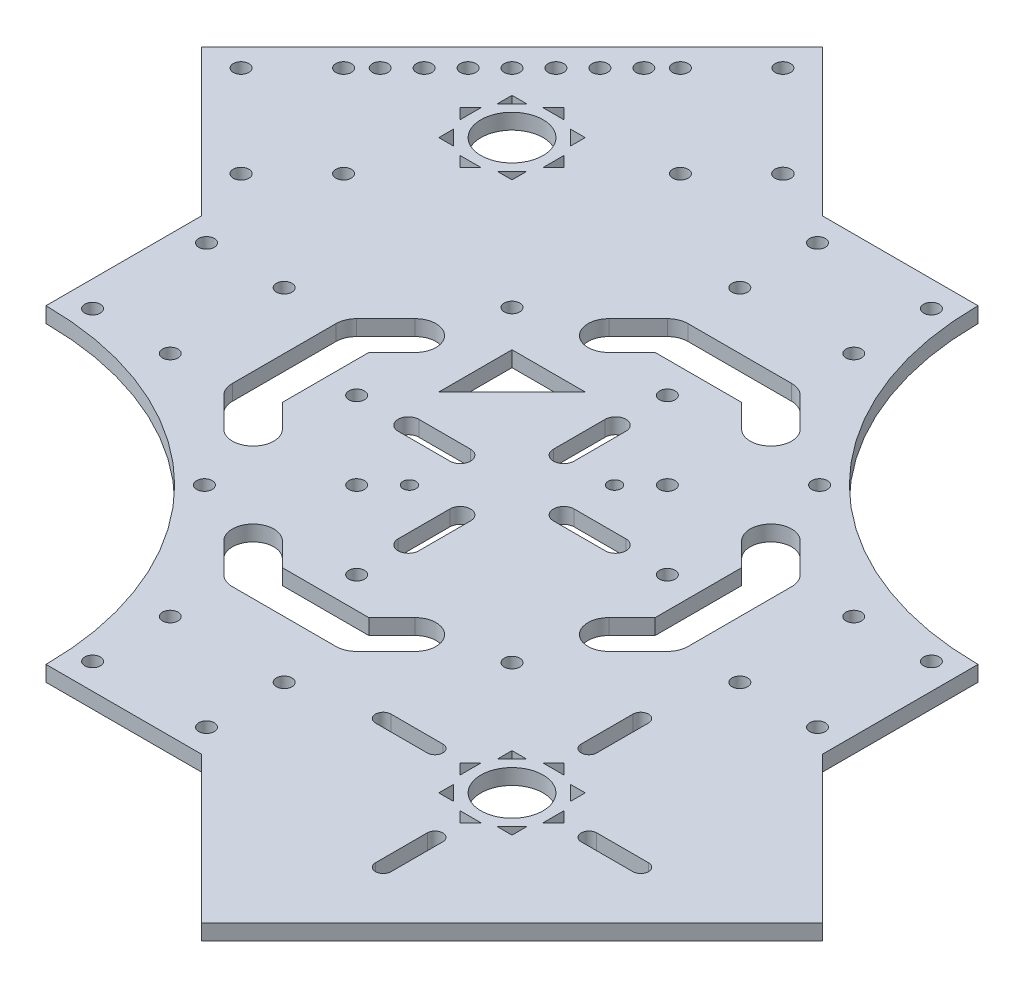
SolidWorks part; units mm, degrees
ref_plane "前视基准面" through (0, 0, 0) normal (0, 0, 1) x (1, 0, 0)
ref_plane "上视基准面" through (0, 0, 0) normal (0, 1, 0) x (1, 0, 0)
ref_plane "右视基准面" through (0, 0, 0) normal (1, 0, 0) x (0, 0, -1)
sketch "草图1" plane through (0, 0, 0) normal (0, 1, 0) x (1, 0, 0)
  line L0 (0, 0) -> (0, 75)
  line L1 (0, 0) -> (75, 0)
  line L2 (0, 0) -> (0, -75)
  line L3 (0, 0) -> (-75, 0)
  line L4 (0, 75) -> (15, 75)
  line L5 (0, 75) -> (-15, 75)
  line L6 (75, 0) -> (75, 15)
  line L7 (75, 0) -> (75, -15)
  line L8 (0, -75) -> (15, -75)
  line L9 (0, -75) -> (-15, -75)
  line L10 (-75, 0) -> (-75, -15)
  line L11 (-75, 0) -> (-75, 15)
  line L12 (75, 0) -> (70, 0)
  arc A0 (-75, 15) -> (-15, 75) centre (-75, 75) ccw
  arc A1 (15, 75) -> (75, 15) centre (75, 75) ccw
  arc A2 (75, -15) -> (15, -75) centre (75, -75) ccw
  arc A3 (-15, -75) -> (-75, -15) centre (-75, -75) ccw
  circle A4 centre (-11, 70) radius 1.25
  circle A5 centre (11, 70) radius 1.25
  circle A6 centre (70, -11) radius 1.25
  circle A7 centre (70, 11) radius 1.25
  circle A8 centre (-11, -70) radius 1.25
  circle A9 centre (11, -70) radius 1.25
  circle A10 centre (-70, 11) radius 1.25
  circle A11 centre (-70, -11) radius 1.25
  point P9 (0, 0)
  point P21 (0, 0)
  point P32 (0, 0)
  point P35 (0, 0)
  point P44 (0, 0)
  dimension "D1" = 4
extrude "凸台-拉伸1" add sketch "草图1" along normal blind 3 contours A2 L7 L1 L2 L8 A9 A6 | A3 L9 L2 L3 L10 A11 A8 | A0 L11 L3 L0 L5 A4 A10 | A1 L4 L0 L1 L6 A7 A5 region at (-25.2829, 0, -25.2829) region at (25.2829, 0, -25.2829) region at (25.2829, 0, 25.2829) region at (-25.2829, 0, 25.2829)
sketch "草图2" plane through (0, 0, 0) normal (0, -1, 0) x (1, 0, 0)
  line L0 (0, 0) -> (-32.5736, -32.5736)
  line L1 (0, 0) -> (32.5736, -32.5736)
  line L2 (-31.4663, 0.3536) -> (-0.3536, 31.4663)
  line L3 (31.4663, -0.3536) -> (-0.3536, 31.4663)
  line L4 (0.3536, -31.4663) -> (31.4663, -0.3536)
  line L5 (0.3536, -31.4663) -> (-31.4663, 0.3536)
  arc A0 (-15, -75) -> (-75, -15) centre (-75, -75) ccw construction
  circle A2 centre (0.3536, -31.4663) radius 1.5
  circle A3 centre (31.4663, -0.3536) radius 1.5
  circle A4 centre (-0.3536, 31.4663) radius 1.5
  circle A5 centre (-31.4663, 0.3536) radius 1.5
  point P12 (-15.5563, -15.5563)
  point P16 (-15.9099, 15.9099)
  point P17 (15.9099, -15.9099)
extrude "切除-拉伸1" cut sketch "草图2" against normal blind 3 contours A3 | A2 | A5 | A4
sketch "草图3" plane through (0, 3, 0) normal (0, 1, 0) x (1, 0, 0)
  line L0 (0.3536, 31.4663) -> (-31.4663, -0.3536)
  line L1 (-15.5563, 15.5563) -> (-22.6274, 22.6274)
  line L2 (-15.5563, 15.5563) -> (-12.0208, 19.0919)
  line L3 (-15.5563, 15.5563) -> (-19.0919, 12.0208)
  line L4 (-19.0919, 12.0208) -> (-22.6274, 22.6274)
  line L5 (-12.0208, 19.0919) -> (-22.6274, 22.6274)
extrude "切除-拉伸2" cut sketch "草图3" against normal blind 3 contours L0 L5 L1 | L4 L0 L1 region at (-16.7349, 3, -19.0919) region at (-19.0919, 3, -16.7349)
sketch "草图4" plane through (0, 3, 0) normal (0, 1, 0) x (1, 0, 0)
  line L0 (31.4663, 0.3536) -> (-0.3536, -31.4663)
  line L1 (0, 0) -> (21.2132, -21.2132)
  line L2 (28.2843, -14.1421) -> (14.1421, -28.2843)
  line L3 (14.1421, -28.2843) -> (28.2843, -14.1421) construction
  line L4 (8.4817, -22.6239) -> (22.6239, -8.4817)
  line L5 (19.8025, -33.9447) -> (33.9447, -19.8025)
  arc A0 (8.4817, -22.6239) -> (19.8025, -33.9447) centre (14.1421, -28.2843) ccw
  arc A1 (33.9447, -19.8025) -> (22.6239, -8.4817) centre (28.2843, -14.1421) ccw
  point P9 (21.2132, -21.2132)
extrude "切除-拉伸3" cut sketch "草图4" against normal blind 3 contours L5 A1 L0 A0 region at (21.2143, 3, 21.2143)
sketch "草图5" plane through (0, 3, 0) normal (0, 1, 0) x (1, 0, 0)
  line L0 (-12.0208, 19.0919) -> (-8.4853, 22.6274)
  line L1 (-8.4853, 22.6274) -> (-22.6274, 22.6274)
  line L2 (-19.0919, 12.0208) -> (-22.6274, 8.4853)
  line L3 (-22.6274, 8.4853) -> (-22.6274, 22.6274)
  line L4 (-12.0208, 19.0919) -> (-22.6274, 22.6274)
  line M28 (-19.0919, 12.0208) -> (-22.6274, 22.6274)
extrude "切除-拉伸4" cut sketch "草图5" against normal blind 10 contours L3 L2 M28 | L4 L0 L1 region at (-21.4489, 3, -14.3778)
sketch "草图6" plane through (0, 3, 0) normal (0, 1, 0) x (1, 0, 0)
  line L0 (0, 0) -> (-28.2843, -28.2843)
  line L1 (-28.2843, -28.2843) -> (-35.3553, -21.2132)
  line L2 (0, 0) -> (-22.6274, 22.6274)
  circle A0 centre (-35.3553, -21.2132) radius 1.5
  circle A1 centre (-21.2132, -35.3553) radius 1.5
  circle A2 centre (35.3553, 21.2132) radius 1.5
  circle A3 centre (21.2132, 35.3553) radius 1.5
extrude "切除-拉伸5" cut sketch "草图6" against normal blind 10 contours A1 | A0 | A2 | A3
sketch "草图7" plane through (0, 3, 0) normal (0, 1, 0) x (1, 0, 0)
  circle A0 centre (-29.6985, 29.6985) radius 1.5
  circle A1 centre (29.6985, 29.6985) radius 1.5
  circle A2 centre (29.6985, -29.6985) radius 1.5
  circle A3 centre (-29.6985, -29.6985) radius 1.5
  point P11 (0, 0)
  dimension "D1" = 4
extrude "切除-拉伸8" cut sketch "草图7" against normal blind 10
sketch "草图8" plane through (0, 3, 0) normal (0, 1, 0) x (1, 0, 0)
  circle A0 centre (-11, 55) radius 1.5
  circle A1 centre (11, 55) radius 1.5
  circle A2 centre (55, 11) radius 1.5
  circle A3 centre (55, -11) radius 1.5
  circle A4 centre (11, -55) radius 1.5
  circle A5 centre (-11, -55) radius 1.5
  circle A6 centre (-55, -11) radius 1.5
  circle A7 centre (-55, 11) radius 1.5
  point P21 (0, 0)
  dimension "D1" = 4
extrude "切除-拉伸9" cut sketch "草图8" against normal blind 10
sketch "草图9" plane through (0, 3, 0) normal (0, 1, 0) x (1, 0, 0)
  circle A0 centre (0, 0) radius 15
extrude "切除-拉伸10" cut sketch "草图9" against normal blind 10
sketch "草图11" plane through (0, 3, 0) normal (0, 1, 0) x (1, 0, 0)
  circle A0 centre (-35.3553, -21.2132) radius 1.5
  circle A2 centre (35.3553, 21.2132) radius 1.5
  circle A3 centre (21.2132, 35.3553) radius 1.5
  circle A4 centre (0.3536, 31.4663) radius 1.5
  circle A5 centre (31.4663, 0.3536) radius 1.5
  circle A6 centre (-0.3536, -31.4663) radius 1.5
  circle A7 centre (-31.4663, -0.3536) radius 1.5
  circle A8 centre (-21.2132, -35.3553) radius 1.5
extrude "凸台-拉伸3" add sketch "草图11" against normal blind 3
sketch "草图12" plane through (0, 3, 0) normal (0, 1, 0) x (1, 0, 0)
  line L0 (0, 0) -> (-40, 0)
  line L1 (-40, 0) -> (-40, 10)
  line L2 (-40, 0) -> (-40, -10)
  line L3 (-40, -10) -> (-40, 10) construction
  line L4 (-44, -10) -> (-44, 10)
  line L5 (-36, -10) -> (-36, 10)
  line L6 (-10, 40) -> (10, 40) construction
  line L7 (-10, 44) -> (10, 44)
  line L8 (-10, 36) -> (10, 36)
  line L9 (40, 10) -> (40, -10) construction
  line L10 (44, 10) -> (44, -10)
  line L11 (36, 10) -> (36, -10)
  line L12 (10, -40) -> (-10, -40) construction
  line L13 (10, -44) -> (-10, -44)
  line L14 (10, -36) -> (-10, -36)
  arc A0 (-44, -10) -> (-36, -10) centre (-40, -10) ccw
  arc A1 (-36, 10) -> (-44, 10) centre (-40, 10) ccw
  arc A2 (-10, 44) -> (-10, 36) centre (-10, 40) ccw
  arc A3 (10, 36) -> (10, 44) centre (10, 40) ccw
  arc A4 (44, 10) -> (36, 10) centre (40, 10) ccw
  arc A5 (36, -10) -> (44, -10) centre (40, -10) ccw
  arc A6 (10, -44) -> (10, -36) centre (10, -40) ccw
  arc A7 (-10, -36) -> (-10, -44) centre (-10, -40) ccw
  point P3 (-40, 0)
  point P13 (0, 40)
  point P20 (40, 0)
  point P27 (0, -40)
  point P34 (0, 0)
  dimension "D1" = 4
extrude "切除-拉伸12" cut sketch "草图12" against normal blind 3 contours L5 A1 L4 A0 | L8 A3 L7 A2 | L11 A5 L10 A4 | L14 A7 L13 A6 region at (-43.7088, 3, 0) region at (0, 3, -40) region at (40, 3, 0) region at (0, 3, 40)
sketch "草图14" plane through (0, 3, 0) normal (0, 1, 0) x (1, 0, 0)
  line L0 (22.8277, -8.285) -> (8.285, -22.8277) construction
  line L1 (19.8025, -33.9447) -> (33.9447, -19.8025) construction
  line L2 (8.285, -22.8277) -> (22.8277, -8.285)
  line L3 (22.8277, -8.285) -> (19.8025, -33.9447)
  line L4 (19.8025, -33.9447) -> (33.9447, -19.8025)
  arc A0 (8.285, -22.8277) -> (19.8025, -33.9447) centre (14.1421, -28.2843) ccw
  arc A1 (8.285, -22.8277) -> (19.8025, -33.9447) centre (14.1421, -28.2843) ccw construction
  arc A2 (33.9447, -19.8025) -> (22.8277, -8.285) centre (28.2843, -14.1421) ccw construction
  arc A3 (22.8277, -8.285) -> (32.1857, -7.1522) centre (28.2843, -14.1421) ccw
  circle A4 centre (28.2843, -14.1421) radius 8.005
extrude "凸台-拉伸4" add sketch "草图14" against normal blind 3 contours A3 A4 L3 | L2 A3 L3 | A3 L2 A0 L3 | A3 L3 L4 region at (14.6624, 3, 25.7239) region at (21.4582, 3, 13.3381) region at (24.21, 3, 25.4431) region at (28.7736, 3, 14.1998)
sketch "草图15" plane through (0, 3, 0) normal (0, 1, 0) x (1, 0, 0)
  circle A0 centre (0, 0) radius 15
extrude "凸台-拉伸5" add sketch "草图15" against normal blind 3
sketch "草图17" plane through (0, 3, 0) normal (0, 1, 0) x (1, 0, 0)
  line L0 (0, 0) -> (0, -20)
  line L1 (0, -20) -> (0, -10) construction
  line L2 (-2, -20) -> (-2, -10)
  line L3 (2, -20) -> (2, -10)
  line L4 (-20, 0) -> (-10, 0) construction
  line L5 (-20, 2) -> (-10, 2)
  line L6 (-20, -2) -> (-10, -2)
  line L7 (0, 20) -> (0, 10) construction
  line L8 (2, 20) -> (2, 10)
  line L9 (-2, 20) -> (-2, 10)
  line L10 (20, 0) -> (10, 0) construction
  line L11 (20, -2) -> (10, -2)
  line L12 (20, 2) -> (10, 2)
  arc A0 (-2, -20) -> (2, -20) centre (0, -20) ccw
  arc A1 (2, -10) -> (-2, -10) centre (0, -10) ccw
  arc A2 (-20, 2) -> (-20, -2) centre (-20, 0) ccw
  arc A3 (-10, -2) -> (-10, 2) centre (-10, 0) ccw
  arc A4 (2, 20) -> (-2, 20) centre (0, 20) ccw
  arc A5 (-2, 10) -> (2, 10) centre (0, 10) ccw
  arc A6 (20, -2) -> (20, 2) centre (20, 0) ccw
  arc A7 (10, 2) -> (10, -2) centre (10, 0) ccw
  point P3 (0, -15)
  point P13 (-15, 0)
  point P20 (0, 15)
  point P27 (15, 0)
  point P33 (0, 0)
  dimension "D1" = 4
extrude "切除-拉伸13" cut sketch "草图17" against normal blind 3 contours L8 A5 L9 A4 | L12 A7 L11 A6 | L3 A1 L2 A0 | L5 A3 L6 A2
sketch "草图18" plane through (0, 3, 0) normal (0, 1, 0) x (1, 0, 0)
  line L0 (0, 0) -> (-32.5736, 32.5736)
  line L1 (-32.5736, 32.5736) -> (-46.7157, 46.7157)
  line L2 (-50.2513, 50.2513) -> (-61.9773, 38.5252)
  line L3 (-46.7157, 46.7157) -> (-50.2513, 50.2513)
  line L4 (-61.9773, 38.5252) -> (-38.5252, 61.9773)
  line L5 (-38.5252, 61.9773) -> (-22.5002, 45.9523)
  line L6 (-61.9773, 38.5252) -> (-45.9523, 22.5002)
  arc A0 (-75, 15) -> (-15, 75) centre (-75, 75) ccw construction
  circle A1 centre (-67.9289, 67.9289) radius 30
  circle A2 centre (-75, 75) radius 60
extrude "凸台-拉伸7" add sketch "草图18" against normal blind 3 contours L4 A1 L2 | L2 A1 L3 | L3 A1 L4 | L6 A2 L1 A1 | L1 A2 L5 A1 region at (-46.4984, 3, -34.5306) region at (-34.5306, 3, -46.4984) region at (-53.277, 3, -44.3758) region at (-44.3758, 3, -53.277) region at (-68.7208, 3, -68.7208)
sketch "草图19" plane through (0, 3, 0) normal (0, 1, 0) x (1, 0, 0)
  line L0 (-61.9773, 38.5252) -> (-38.5252, 61.9773)
  line L1 (-50.2513, 50.2513) -> (-36.1091, 36.1091)
  line L2 (-36.1091, 36.1091) -> (-43.1802, 29.0381)
  line L3 (-36.1091, 36.1091) -> (-29.0381, 43.1802)
  line L4 (-29.0381, 43.1802) -> (-37.1408, 51.2829)
  line L5 (-37.1408, 51.2829) -> (-51.2829, 37.1408)
  line L6 (-51.2829, 37.1408) -> (-43.1802, 29.0381)
  circle A1 centre (-67.9289, 67.9289) radius 35
  circle A2 centre (-67.9289, 67.9289) radius 45
extrude "切除-拉伸14" cut sketch "草图19" against normal blind 3 contours L1 A2 L4 A1 | L6 A2 L1 A1 region at (-36.3949, 3, -43.5045) region at (-43.5045, 3, -36.3949)
sketch "草图21" plane through (0, 3, 0) normal (0, 1, 0) x (1, 0, 0)
  line L0 (-61.9773, 38.5252) -> (-38.5252, 61.9773)
  line L1 (-67.9289, 67.9289) -> (-53.7868, 53.7868)
  line L2 (-82.0711, 82.0711) -> (-75, 75)
  line L3 (-67.9289, 67.9289) -> (-82.0711, 82.0711)
  line L4 (-53.7868, 53.7868) -> (-60.8579, 60.8579)
  line L5 (-82.0711, 82.0711) -> (-75, 75) construction
  line L6 (-81.1872, 82.955) -> (-74.1161, 75.8839)
  line L7 (-82.955, 81.1872) -> (-75.8839, 74.1161)
  line L8 (-60.8579, 60.8579) -> (-53.7868, 53.7868) construction
  line L9 (-59.974, 61.7417) -> (-52.9029, 54.6707)
  line L10 (-61.7417, 59.974) -> (-54.6707, 52.9029)
  arc A0 (-81.1872, 82.955) -> (-82.955, 81.1872) centre (-82.0711, 82.0711) ccw
  arc A1 (-75.8839, 74.1161) -> (-74.1161, 75.8839) centre (-75, 75) ccw
  arc A2 (-59.974, 61.7417) -> (-61.7417, 59.974) centre (-60.8579, 60.8579) ccw
  arc A3 (-54.6707, 52.9029) -> (-52.9029, 54.6707) centre (-53.7868, 53.7868) ccw
  point P2 (-78.5355, 78.5355)
  point P15 (-57.3223, 57.3223)
extrude "切除-拉伸15" cut sketch "草图21" against normal blind 3 contours A1 L6 A0 L7 | A3 L9 A2 L10 region at (-75, 3, -73.8854)
pattern_circular "阵列(圆周)1" count 8 over 360 about axis through (-67.9289, 3, -67.9289) along (0, 1, 0) of "切除-拉伸15"
sketch "草图22" plane through (0, 3, 0) normal (0, 1, 0) x (1, 0, 0)
  line L0 (0, 0) -> (9.8995, 9.8995)
  line L1 (0, 0) -> (-9.8995, -9.8995)
  circle A0 centre (9.8995, 9.8995) radius 1.25
  circle A1 centre (-9.8995, -9.8995) radius 1.25
extrude "切除-拉伸17" cut sketch "草图22" against normal blind 3 contours A0 | A1
sketch "草图23" plane through (0, 3, 0) normal (0, 1, 0) x (1, 0, 0)
  circle A0 centre (0, 30) radius 1.5
  circle A1 centre (30, 0) radius 1.5
  circle A2 centre (0, -30) radius 1.5
  circle A3 centre (-30, 0) radius 1.5
  point P13 (0, 0)
  dimension "D1" = 4
extrude "切除-拉伸18" cut sketch "草图23" against normal blind 10
sketch "草图24" plane through (0, 3, 0) normal (0, 1, 0) x (1, 0, 0)
  circle A0 centre (-15, -15) radius 1.5
  circle A1 centre (15, 15) radius 1.5
extrude "切除-拉伸19" cut sketch "草图24" against normal blind 10
sketch "草图25" plane through (0, 3, 0) normal (0, 1, 0) x (1, 0, 0)
  circle A0 centre (-75, 75) radius 60
extrude "切除-拉伸20" cut sketch "草图25" against normal blind 10
sketch "草图26" plane through (0, 3, 0) normal (0, 1, 0) x (1, 0, 0)
  line L0 (-15, 75) -> (-75, 15)
  circle A0 centre (-75, 75) radius 60
extrude "凸台-拉伸8" add sketch "草图26" against normal blind 3 contours L0 A0 region at (-39.9612, 3, -39.9612)
sketch "草图27" plane through (0, 0, 0) normal (0, -1, 0) x (1, 0, 0)
  line L0 (-45, -45) -> (-23.5998, -66.4002)
  line L1 (-15, -75) -> (-75, -15) construction
  line L2 (-23.5998, -66.4002) -> (-66.0262, -23.9738)
  line L3 (-15, -75) -> (-22.0711, -82.0711)
  line L4 (-22.0711, -82.0711) -> (-75, -15)
  line L5 (-75, -15) -> (-82.0711, -22.0711)
  line L6 (-82.0711, -22.0711) -> (-22.0711, -82.0711)
  line L7 (75, 15) -> (15, 75)
  line L8 (15, 75) -> (22.0711, 82.0711)
  line L9 (75, 15) -> (82.0711, 22.0711)
  line L10 (82.0711, 22.0711) -> (22.0711, 82.0711)
  line L11 (-15, -75) -> (-75, -15)
  line L12 (-22.0711, -82.0711) -> (-29.1421, -89.1421)
  line L13 (-29.1421, -89.1421) -> (-82.0711, -22.0711)
  line L14 (-82.0711, -22.0711) -> (-89.1421, -29.1421)
  line L15 (-89.1421, -29.1421) -> (-29.1421, -89.1421)
  circle A0 centre (75, 75) radius 60
extrude "凸台-拉伸10" add sketch "草图27" against normal blind 3 contours L14 L15 L13 | L13 L12 L6 | L5 L6 L4 | L3 L11 L0 L2 L4 region at (-37.357, 0, -57.357) region at (-59.714, 0, -39.714) region at (-44.4281, 0, -64.4281) region at (-66.7851, 0, -46.7851)
sketch "草图28" plane through (0, 0, 0) normal (0, -1, 0) x (1, 0, 0)
  line L0 (-59.1421, -59.1421) -> (-52.0711, -52.0711)
  line L1 (-89.1421, -29.1421) -> (-29.1421, -89.1421) construction
  line L2 (-52.0711, -52.0711) -> (-25.9081, -78.234)
  line L3 (-52.0711, -52.0711) -> (-78.234, -25.9081)
  line L4 (11, -70) -> (8.198, -68.4493)
  circle A1 centre (11, -70) radius 1.5
  circle A2 centre (-11, -70) radius 1.5
  circle A3 centre (-70, -11) radius 1.5
  circle A4 centre (-70, 11) radius 1.5
  circle A5 centre (-11, 70) radius 1.5
  circle A6 centre (11, 70) radius 1.5
  circle A7 centre (70, 11) radius 1.5
  circle A8 centre (70, -11) radius 1.5
  circle A9 centre (-25.9081, -78.234) radius 1.54
  circle A10 centre (-78.234, -25.9081) radius 1.52
extrude "切除-拉伸21" cut sketch "草图28" against normal blind 3 contours A9 | A10 | A3 | A4 | A2 | A1 | A8 | A7 | A5 | A6 region at (-25.3355, 0, -76.8515) region at (-79.5986, 0, -25.3429)
sketch "草图29" plane through (0, 0, 0) normal (0, -1, 0) x (1, 0, 0)
  line L0 (-59.1421, -59.1421) -> (-22.6274, -22.6274)
  line L1 (-78.234, -25.9081) -> (-68.3345, -35.8076)
  line L2 (-89.1421, -29.1421) -> (-29.1421, -89.1421) construction
  circle A0 centre (-68.3345, -35.8076) radius 1.5
  circle A1 centre (-35.8076, -68.3345) radius 1.5
extrude "切除-拉伸22" cut sketch "草图29" against normal blind 3 contours A1 | A0
sketch "草图30" plane through (0, 0, 0) normal (0, -1, 0) x (1, 0, 0)
  line L0 (-29.1421, -89.1421) -> (-89.1421, -29.1421)
  line L1 (-29.1421, -89.1421) -> (-43.2843, -103.2843)
  line L2 (-89.1421, -29.1421) -> (-103.2843, -43.2843)
  line L3 (-43.2843, -103.2843) -> (-103.2843, -43.2843)
extrude "凸台-拉伸11" add sketch "草图30" against normal blind 3
sketch "草图31" plane through (0, 0, 0) normal (0, -1, 0) x (1, 0, 0)
  line L1 (-25.9081, -78.234) -> (-78.234, -25.9081)
  circle A0 centre (-43.5858, -95.9117) radius 1.5
  circle A1 centre (-53.4853, -86.0122) radius 1.5
  circle A2 centre (-86.0122, -53.4853) radius 1.5
  circle A3 centre (-95.9117, -43.5858) radius 1.5
extrude "切除-拉伸23" cut sketch "草图31" against normal blind 3 contours A0 | A1 | A2 | A3
sketch "草图32" plane through (0, 0, 0) normal (0, -1, 0) x (1, 0, 0)
  line L0 (75, 15) -> (15, 75)
  line L1 (75, 15) -> (15, 75)
  line L2 (75, 15) -> (89.1421, 29.1421)
  line L3 (15, 75) -> (29.1421, 89.1421)
  line L4 (89.1421, 29.1421) -> (29.1421, 89.1421)
  circle A0 centre (75, 75) radius 60
extrude "凸台-拉伸12" add sketch "草图32" against normal blind 3 contours L0 A0 | L2 L4 L3 L0 region at (39.9612, 0, 39.9612) region at (52.0711, 0, 52.0711)
sketch "草图33" plane through (0, 0, 0) normal (0, -1, 0) x (-1, 0, 0)
  line L0 (-29.6985, -29.6985) -> (-59.1421, -59.1421)
  line L1 (-89.1421, -29.1421) -> (-29.1421, -89.1421) construction
  line L2 (-44.4203, -44.4203) -> (-14.6894, -44.4203)
  line L3 (-14.6894, -44.4203) -> (-44.4203, -16.8394)
  line L4 (-44.4203, -16.8394) -> (-44.4203, -44.4203)
  line L5 (-29.5549, -44.4203) -> (-19.5549, -44.4203) construction
  line L6 (-29.5549, -42.92) -> (-19.5549, -42.92)
  line L7 (-29.5549, -45.9207) -> (-19.5549, -45.9207)
  line L8 (-44.4203, -59.2858) -> (-44.4203, -69.2858) construction
  line L9 (-42.92, -59.2858) -> (-42.92, -69.2858)
  line L10 (-45.9207, -59.2858) -> (-45.9207, -69.2858)
  line L11 (-59.2858, -44.4203) -> (-69.2858, -44.4203) construction
  line L12 (-59.2858, -45.9207) -> (-69.2858, -45.9207)
  line L13 (-59.2858, -42.92) -> (-69.2858, -42.92)
  line L14 (-44.4203, -29.5549) -> (-44.4203, -19.5549) construction
  line L15 (-45.9207, -29.5549) -> (-45.9207, -19.5549)
  line L16 (-42.92, -29.5549) -> (-42.92, -19.5549)
  arc A0 (-29.5549, -42.92) -> (-29.5549, -45.9207) centre (-29.5549, -44.4203) ccw
  arc A1 (-19.5549, -45.9207) -> (-19.5549, -42.92) centre (-19.5549, -44.4203) ccw
  arc A2 (-42.92, -59.2858) -> (-45.9207, -59.2858) centre (-44.4203, -59.2858) ccw
  arc A3 (-45.9207, -69.2858) -> (-42.92, -69.2858) centre (-44.4203, -69.2858) ccw
  arc A4 (-59.2858, -45.9207) -> (-59.2858, -42.92) centre (-59.2858, -44.4203) ccw
  arc A5 (-69.2858, -42.92) -> (-69.2858, -45.9207) centre (-69.2858, -44.4203) ccw
  arc A6 (-45.9207, -29.5549) -> (-42.92, -29.5549) centre (-44.4203, -29.5549) ccw
  arc A7 (-42.92, -19.5549) -> (-45.9207, -19.5549) centre (-44.4203, -19.5549) ccw
  point P10 (-24.5549, -44.4203)
  point P20 (-44.4203, -64.2858)
  point P27 (-64.2858, -44.4203)
  point P34 (-44.4203, -24.5549)
  point P39 (-44.4203, -44.4203)
  dimension "D1" = 4
extrude "切除-拉伸24" cut sketch "草图33" against normal blind 3 contours L10 A3 L9 A2 | L7 A1 L6 A0 | L12 A5 L13 A4 | L15 A7 L16 A6
sketch "草图34" plane through (0, 0, 0) normal (0, -1, 0) x (1, 0, 0)
  line L0 (29.1421, 89.1421) -> (89.1421, 29.1421)
  line L1 (29.1421, 89.1421) -> (43.2843, 103.2843)
  line L2 (89.1421, 29.1421) -> (103.2843, 43.2843)
  line L3 (43.2843, 103.2843) -> (103.2843, 43.2843)
  line L4 (75, 15) -> (89.1421, 29.1421) construction
  line L5 (89.1421, 29.1421) -> (29.1421, 89.1421) construction
extrude "凸台-拉伸13" add sketch "草图34" against normal blind 3
sketch "草图35" plane through (0, 0, 0) normal (0, -1, 0) x (1, 0, 0)
  line L0 (10, 40) -> (15.6569, 34.3431)
  line L1 (10, 40) -> (15.6569, 34.3431) construction
  line L2 (12.8284, 42.8284) -> (18.4853, 37.1716)
  line L3 (7.1716, 37.1716) -> (12.8284, 31.5147)
  line L4 (-10, 40) -> (-15.6569, 34.3431) construction
  line L5 (-7.1716, 37.1716) -> (-12.8284, 31.5147)
  line L6 (-12.8284, 42.8284) -> (-18.4853, 37.1716)
  line L7 (40, -10) -> (34.3431, -15.6569) construction
  line L8 (42.8284, -12.8284) -> (37.1716, -18.4853)
  line L9 (37.1716, -7.1716) -> (31.5147, -12.8284)
  line L10 (40, 10) -> (34.3431, 15.6569) construction
  line L11 (37.1716, 7.1716) -> (31.5147, 12.8284)
  line L12 (42.8284, 12.8284) -> (37.1716, 18.4853)
  line L13 (-10, -40) -> (-15.6569, -34.3431) construction
  line L14 (-12.8284, -42.8284) -> (-18.4853, -37.1716)
  line L15 (-7.1716, -37.1716) -> (-12.8284, -31.5147)
  line L16 (10, -40) -> (15.6569, -34.3431) construction
  line L17 (7.1716, -37.1716) -> (12.8284, -31.5147)
  line L18 (12.8284, -42.8284) -> (18.4853, -37.1716)
  line L19 (-40, 10) -> (-34.3431, 15.6569) construction
  line L20 (-42.8284, 12.8284) -> (-37.1716, 18.4853)
  line L21 (-37.1716, 7.1716) -> (-31.5147, 12.8284)
  line L22 (-40, -10) -> (-34.3431, -15.6569) construction
  line L23 (-37.1716, -7.1716) -> (-31.5147, -12.8284)
  line L24 (-42.8284, -12.8284) -> (-37.1716, -18.4853)
  arc A0 (12.8284, 42.8284) -> (7.1716, 37.1716) centre (10, 40) ccw
  arc A1 (12.8284, 31.5147) -> (18.4853, 37.1716) centre (15.6569, 34.3431) ccw
  arc A2 (-7.1716, 37.1716) -> (-12.8284, 42.8284) centre (-10, 40) ccw
  arc A3 (-18.4853, 37.1716) -> (-12.8284, 31.5147) centre (-15.6569, 34.3431) ccw
  arc A4 (42.8284, -12.8284) -> (37.1716, -7.1716) centre (40, -10) ccw
  arc A5 (31.5147, -12.8284) -> (37.1716, -18.4853) centre (34.3431, -15.6569) ccw
  arc A6 (37.1716, 7.1716) -> (42.8284, 12.8284) centre (40, 10) ccw
  arc A7 (37.1716, 18.4853) -> (31.5147, 12.8284) centre (34.3431, 15.6569) ccw
  arc A8 (-12.8284, -42.8284) -> (-7.1716, -37.1716) centre (-10, -40) ccw
  arc A9 (-12.8284, -31.5147) -> (-18.4853, -37.1716) centre (-15.6569, -34.3431) ccw
  arc A10 (7.1716, -37.1716) -> (12.8284, -42.8284) centre (10, -40) ccw
  arc A11 (18.4853, -37.1716) -> (12.8284, -31.5147) centre (15.6569, -34.3431) ccw
  arc A12 (-42.8284, 12.8284) -> (-37.1716, 7.1716) centre (-40, 10) ccw
  arc A13 (-31.5147, 12.8284) -> (-37.1716, 18.4853) centre (-34.3431, 15.6569) ccw
  arc A14 (-37.1716, -7.1716) -> (-42.8284, -12.8284) centre (-40, -10) ccw
  arc A15 (-37.1716, -18.4853) -> (-31.5147, -12.8284) centre (-34.3431, -15.6569) ccw
  point P3 (12.8284, 37.1716)
  point P11 (-12.8284, 37.1716)
  point P21 (37.1716, -12.8284)
  point P28 (37.1716, 12.8284)
  point P35 (-12.8284, -37.1716)
  point P42 (12.8284, -37.1716)
  point P49 (-37.1716, 12.8284)
  point P56 (-37.1716, -12.8284)
  point P61 (0, 0)
  dimension "D1" = 4
extrude "切除-拉伸25" cut sketch "草图35" against normal blind 10 contours L12 A7 L11 A6 | L3 A1 L2 A0 | L6 A3 L5 A2 | L21 A13 L20 A12 | L24 A15 L23 A14 | L15 A9 L14 A8 | L18 A11 L17 A10 | L9 A5 L8 A4 region at (15.5203, 0, 39.8634) region at (-12.8284, 0, 37.1716) region at (37.1716, 0, -12.8284) region at (37.1716, 0, 12.8284) region at (-12.8284, 0, -37.1716) region at (12.8284, 0, -37.1716) region at (-37.1716, 0, 12.8284) region at (-37.1716, 0, -12.8284)
sketch "草图36" plane through (0, 0, 0) normal (0, -1, 0) x (1, 0, 0)
  line L0 (19.5549, 44.4203) -> (29.5549, 44.4203) construction
  line L1 (19.5549, 45.9203) -> (29.5549, 45.9203)
  line L2 (19.5549, 42.9203) -> (29.5549, 42.9203)
  line L3 (26.6259, 51.4914) -> (36.6259, 51.4914) construction
  line L4 (44.4203, 69.2858) -> (44.4203, 59.2858) construction
  line L5 (45.9203, 69.2858) -> (45.9203, 59.2858)
  line L6 (42.9203, 69.2858) -> (42.9203, 59.2858)
  line L7 (69.2858, 44.4203) -> (59.2858, 44.4203) construction
  line L8 (69.2858, 42.9203) -> (59.2858, 42.9203)
  line L9 (69.2858, 45.9203) -> (59.2858, 45.9203)
  line L10 (44.4203, 19.5549) -> (44.4203, 29.5549) construction
  line L11 (42.9203, 19.5549) -> (42.9203, 29.5549)
  line L12 (45.9203, 19.5549) -> (45.9203, 29.5549)
  line L13 (26.6259, 52.9914) -> (36.6259, 52.9914)
  line L14 (26.6259, 49.9914) -> (36.6259, 49.9914)
  line L15 (51.4914, 76.3568) -> (51.4914, 66.3568) construction
  line L16 (52.9914, 76.3568) -> (52.9914, 66.3568)
  line L17 (49.9914, 76.3568) -> (49.9914, 66.3568)
  line L18 (76.3568, 51.4914) -> (66.3568, 51.4914) construction
  line L19 (76.3568, 49.9914) -> (66.3568, 49.9914)
  line L20 (76.3568, 52.9914) -> (66.3568, 52.9914)
  line L21 (51.4914, 26.6259) -> (51.4914, 36.6259) construction
  line L22 (49.9914, 26.6259) -> (49.9914, 36.6259)
  line L23 (52.9914, 26.6259) -> (52.9914, 36.6259)
  arc A0 (19.5549, 45.9203) -> (19.5549, 42.9203) centre (19.5549, 44.4203) ccw
  arc A1 (29.5549, 42.9203) -> (29.5549, 45.9203) centre (29.5549, 44.4203) ccw
  arc A2 (45.9203, 69.2858) -> (42.9203, 69.2858) centre (44.4203, 69.2858) ccw
  arc A3 (42.9203, 59.2858) -> (45.9203, 59.2858) centre (44.4203, 59.2858) ccw
  arc A4 (69.2858, 42.9203) -> (69.2858, 45.9203) centre (69.2858, 44.4203) ccw
  arc A5 (59.2858, 45.9203) -> (59.2858, 42.9203) centre (59.2858, 44.4203) ccw
  arc A6 (42.9203, 19.5549) -> (45.9203, 19.5549) centre (44.4203, 19.5549) ccw
  arc A7 (45.9203, 29.5549) -> (42.9203, 29.5549) centre (44.4203, 29.5549) ccw
  arc A8 (26.6259, 52.9914) -> (26.6259, 49.9914) centre (26.6259, 51.4914) ccw
  arc A9 (36.6259, 49.9914) -> (36.6259, 52.9914) centre (36.6259, 51.4914) ccw
  arc A10 (52.9914, 76.3568) -> (49.9914, 76.3568) centre (51.4914, 76.3568) ccw
  arc A11 (49.9914, 66.3568) -> (52.9914, 66.3568) centre (51.4914, 66.3568) ccw
  arc A12 (76.3568, 49.9914) -> (76.3568, 52.9914) centre (76.3568, 51.4914) ccw
  arc A13 (66.3568, 52.9914) -> (66.3568, 49.9914) centre (66.3568, 51.4914) ccw
  arc A14 (49.9914, 26.6259) -> (52.9914, 26.6259) centre (51.4914, 26.6259) ccw
  arc A15 (52.9914, 36.6259) -> (49.9914, 36.6259) centre (51.4914, 36.6259) ccw
  point P4 (24.5549, 44.4203)
  point P13 (31.6259, 51.4914)
  point P19 (44.4203, 64.2858)
  point P26 (64.2858, 44.4203)
  point P33 (44.4203, 24.5549)
  point P41 (51.4914, 71.3568)
  point P48 (71.3568, 51.4914)
  point P55 (51.4914, 31.6259)
  dimension "D1" = 2
extrude "切除-拉伸26" cut sketch "草图36" against normal blind 10
sketch "草图37" plane through (0, 0, 0) normal (0, -1, 0) x (1, 0, 0)
  line L0 (44.4203, 69.2858) -> (44.4203, 59.8535) construction
  line L1 (47.888, 69.2858) -> (47.888, 59.8535)
  line L2 (40.9527, 69.2858) -> (40.9527, 59.8535)
  line L3 (60.035, 44.7696) -> (68.5031, 44.7696) construction
  line L4 (60.035, 48.1814) -> (68.5031, 48.1814)
  line L5 (60.035, 41.3579) -> (68.5031, 41.3579)
  line L6 (44.4203, 29.5549) -> (44.4203, 19.6289) construction
  line L7 (48.5122, 29.5549) -> (48.5122, 19.6289)
  line L8 (40.3284, 29.5549) -> (40.3284, 19.6289)
  line L9 (20.3241, 44.7696) -> (29.5195, 44.7696) construction
  line L10 (20.3241, 48.0853) -> (29.5195, 48.0853)
  line L11 (20.3241, 41.454) -> (29.5195, 41.454)
  arc A0 (47.888, 69.2858) -> (40.9527, 69.2858) centre (44.4203, 69.2858) ccw
  arc A1 (40.9527, 59.8535) -> (47.888, 59.8535) centre (44.4203, 59.8535) ccw
  arc A2 (60.035, 48.1814) -> (60.035, 41.3579) centre (60.035, 44.7696) ccw
  arc A3 (68.5031, 41.3579) -> (68.5031, 48.1814) centre (68.5031, 44.7696) ccw
  arc A4 (48.5122, 29.5549) -> (40.3284, 29.5549) centre (44.4203, 29.5549) ccw
  arc A5 (40.3284, 19.6289) -> (48.5122, 19.6289) centre (44.4203, 19.6289) ccw
  arc A6 (20.3241, 48.0853) -> (20.3241, 41.454) centre (20.3241, 44.7696) ccw
  arc A7 (29.5195, 41.454) -> (29.5195, 48.0853) centre (29.5195, 44.7696) ccw
  point P3 (44.4203, 64.5696)
  point P8 (64.2691, 44.7696)
  point P15 (44.4203, 24.5919)
  point P23 (24.9218, 44.7696)
extrude "凸台-拉伸14" add sketch "草图37" against normal blind 3
sketch "草图38" plane through (0, 0, 0) normal (0, -1, 0) x (1, 0, 0)
  line L0 (-52.4533, -52.4533) -> (-53.8675, -51.0391)
  line L1 (-51.0391, -53.8675) -> (-52.4533, -52.4533)
  line L2 (57.1482, 57.1482) -> (55.734, 58.5624)
  line L3 (-53.8675, -51.0391) -> (-51.0391, -51.0391)
  line L4 (-51.0391, -53.8675) -> (-51.0391, -51.0391)
  line L5 (58.5624, 55.734) -> (57.1482, 57.1482)
  line L6 (55.734, 58.5624) -> (58.5624, 58.5624)
  line L7 (58.5624, 55.734) -> (58.5624, 58.5624)
  line L8 (59.4914, 53.4914) -> (61.4914, 51.4914)
  line L9 (59.4914, 49.4914) -> (61.4914, 51.4914)
  line L10 (59.4914, 49.4914) -> (59.4914, 51.4914)
  line L11 (59.4914, 51.4914) -> (59.4914, 53.4914)
  line L12 (58.5624, 47.2487) -> (58.5624, 44.4203)
  line L13 (55.734, 44.4203) -> (58.5624, 44.4203)
  line L14 (55.734, 44.4203) -> (57.1482, 45.8345)
  line L15 (57.1482, 45.8345) -> (58.5624, 47.2487)
  line L16 (53.4914, 43.4914) -> (51.4914, 41.4914)
  line L17 (49.4914, 43.4914) -> (51.4914, 41.4914)
  line L18 (49.4914, 43.4914) -> (51.4914, 43.4914)
  line L19 (51.4914, 43.4914) -> (53.4914, 43.4914)
  line L20 (47.2487, 44.4203) -> (44.4203, 44.4203)
  line L21 (44.4203, 47.2487) -> (44.4203, 44.4203)
  line L22 (44.4203, 47.2487) -> (45.8345, 45.8345)
  line L23 (45.8345, 45.8345) -> (47.2487, 44.4203)
  line L24 (43.4914, 49.4914) -> (41.4914, 51.4914)
  line L25 (43.4914, 53.4914) -> (41.4914, 51.4914)
  line L26 (43.4914, 53.4914) -> (43.4914, 51.4914)
  line L27 (43.4914, 51.4914) -> (43.4914, 49.4914)
  line L28 (44.4203, 55.734) -> (44.4203, 58.5624)
  line L29 (47.2487, 58.5624) -> (44.4203, 58.5624)
  line L30 (47.2487, 58.5624) -> (45.8345, 57.1482)
  line L31 (45.8345, 57.1482) -> (44.4203, 55.734)
  line L32 (49.4914, 59.4914) -> (51.4914, 61.4914)
  line L33 (53.4914, 59.4914) -> (51.4914, 61.4914)
  line L34 (53.4914, 59.4914) -> (51.4914, 59.4914)
  line L35 (51.4914, 59.4914) -> (49.4914, 59.4914)
  line L36 (-50.1102, -56.1102) -> (-48.1102, -58.1102)
  line L37 (-50.1102, -60.1102) -> (-48.1102, -58.1102)
  line L38 (-50.1102, -60.1102) -> (-50.1102, -58.1102)
  line L39 (-50.1102, -58.1102) -> (-50.1102, -56.1102)
  line L40 (-51.0391, -62.3528) -> (-51.0391, -65.1812)
  line L41 (-53.8675, -65.1812) -> (-51.0391, -65.1812)
  line L42 (-53.8675, -65.1812) -> (-52.4533, -63.767)
  line L43 (-52.4533, -63.767) -> (-51.0391, -62.3528)
  line L44 (-56.1102, -66.1102) -> (-58.1102, -68.1102)
  line L45 (-60.1102, -66.1102) -> (-58.1102, -68.1102)
  line L46 (-60.1102, -66.1102) -> (-58.1102, -66.1102)
  line L47 (-58.1102, -66.1102) -> (-56.1102, -66.1102)
  line L48 (-62.3528, -65.1812) -> (-65.1812, -65.1812)
  line L49 (-65.1812, -62.3528) -> (-65.1812, -65.1812)
  line L50 (-65.1812, -62.3528) -> (-63.767, -63.767)
  line L51 (-63.767, -63.767) -> (-62.3528, -65.1812)
  line L52 (-66.1102, -60.1102) -> (-68.1102, -58.1102)
  line L53 (-66.1102, -56.1102) -> (-68.1102, -58.1102)
  line L54 (-66.1102, -56.1102) -> (-66.1102, -58.1102)
  line L55 (-66.1102, -58.1102) -> (-66.1102, -60.1102)
  line L56 (-65.1812, -53.8675) -> (-65.1812, -51.0391)
  line L57 (-62.3528, -51.0391) -> (-65.1812, -51.0391)
  line L58 (-62.3528, -51.0391) -> (-63.767, -52.4533)
  line L59 (-63.767, -52.4533) -> (-65.1812, -53.8675)
  line L60 (-60.1102, -50.1102) -> (-58.1102, -48.1102)
  line L61 (-56.1102, -50.1102) -> (-58.1102, -48.1102)
  line L62 (-56.1102, -50.1102) -> (-58.1102, -50.1102)
  line L63 (-58.1102, -50.1102) -> (-60.1102, -50.1102)
  circle A0 centre (51.4914, 51.4914) radius 6
  circle A1 centre (-58.1102, -58.1102) radius 6
  point P40 (51.4914, 51.4914)
  point P70 (-58.1102, -58.1102)
  dimension "D1" = 2
extrude "切除-拉伸28" cut sketch "草图38" against normal blind 3
sketch "草图39" plane through (0, 0, 0) normal (0, -1, 0) x (1, 0, 0)
  circle A0 centre (-69.7487, -69.7487) radius 1.5
  circle A1 centre (-73.9914, -65.5061) radius 1.5
  circle A2 centre (-78.234, -61.2635) radius 1.5
  circle A3 centre (-82.4767, -57.0208) radius 1.5
  circle A4 centre (-65.5061, -73.9914) radius 1.5
  circle A5 centre (-61.2635, -78.234) radius 1.5
  circle A6 centre (-57.0208, -82.4767) radius 1.5
extrude "切除-拉伸29" cut sketch "草图39" against normal blind 3
